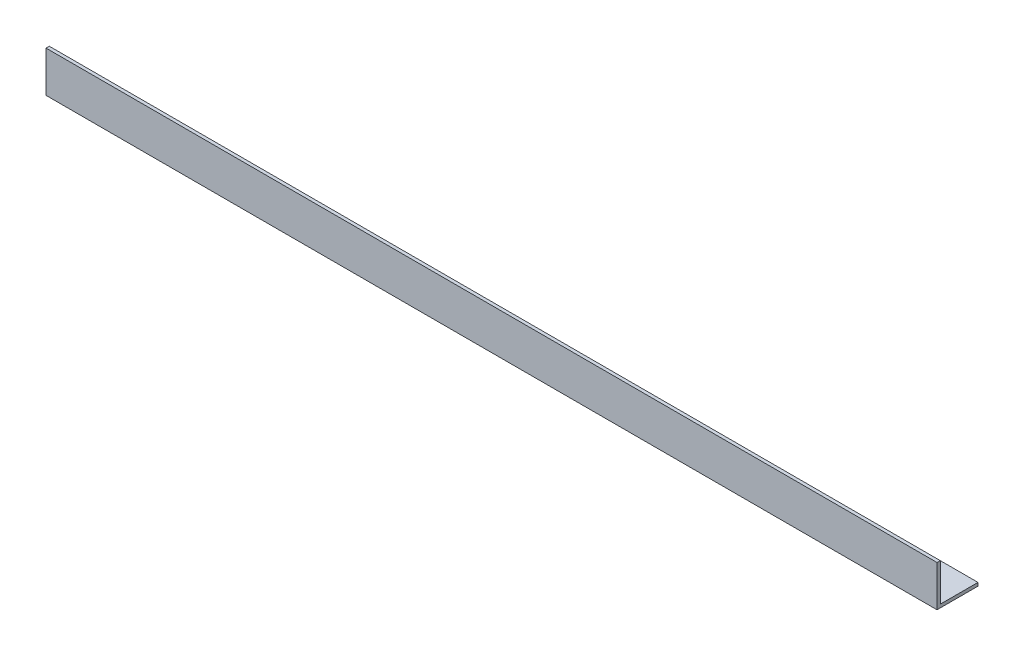
SolidWorks part; units mm, degrees
ref_plane "Спереди" through (0, 0, 0) normal (0, 0, 1) x (1, 0, 0)
ref_plane "Сверху" through (0, 0, 0) normal (0, 1, 0) x (1, 0, 0)
ref_plane "Справа" through (0, 0, 0) normal (1, 0, 0) x (0, 0, -1)
sketch "Эскиз1" plane through (0, 0, 0) normal (1, 0, 0) x (0, 0, -1)
  line L0 (0, 37.7) -> (0, 0)
  line L1 (0, 0) -> (37.7, 0)
extrude "Вытянуть-Тонкостенный1" add sketch "Эскиз1" along normal blind 820 thin thin type one direction reverse wall 3
